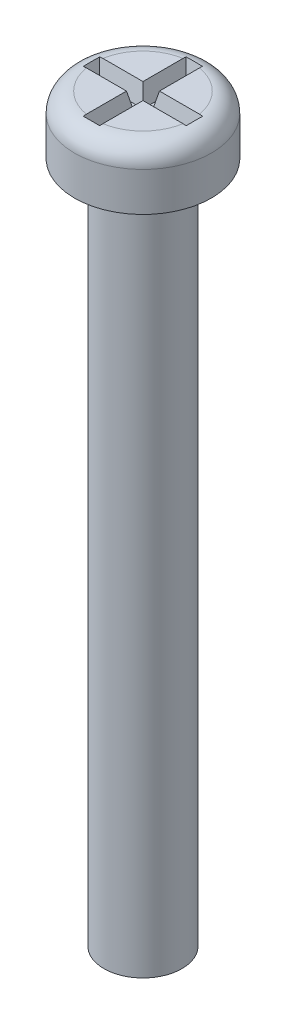
SolidWorks part; units mm, degrees
ref_plane "Спереди" through (0, 0, 0) normal (0, 0, 1) x (1, 0, 0)
ref_plane "Сверху" through (0, 0, 0) normal (0, 1, 0) x (1, 0, 0)
ref_plane "Справа" through (0, 0, 0) normal (1, 0, 0) x (0, 0, -1)
sketch "Эскиз1" plane through (0, 0, 0) normal (0, 1, 0) x (1, 0, 0)
  circle A0 centre (0, 0) radius 2
extrude "Бобышка-Вытянуть1" add sketch "Эскиз1" along normal blind 35
sketch "Эскиз2" plane through (0, 35, 0) normal (0, 1, 0) x (1, 0, 0)
  circle A0 centre (0, 0) radius 3.515
extrude "Бобышка-Вытянуть2" add sketch "Эскиз2" along normal blind 3
sketch "Эскиз3" plane through (0, 38, 0) normal (0, 1, 0) x (1, 0, 0)
  line L0 (-2.6415, 0.4228) -> (-0.4228, 0.4228)
  line L2 (-2.6415, -0.4228) -> (-2.6415, 0.4228)
  line L4 (2.6415, -0.4228) -> (2.6415, 0.4228)
  line L5 (-2.6415, -0.4228) -> (2.6415, 0.4228) construction
  line L6 (-2.6415, 0.4228) -> (2.6415, -0.4228) construction
  line L7 (-0.4228, -2.6415) -> (0.4228, -2.6415)
  line L9 (-0.4228, 2.6415) -> (0.4228, 2.6415)
  line L11 (-0.4228, -2.6415) -> (0.4228, 2.6415) construction
  line L12 (-0.4228, 2.6415) -> (0.4228, -2.6415) construction
  line L13 (-0.4228, 0.4228) -> (-0.4228, 2.6415)
  line L14 (0.4228, 2.6415) -> (0.4228, 0.4228)
  line L15 (0.4228, 0.4228) -> (2.6415, 0.4228)
  line L16 (2.6415, -0.4228) -> (0.4228, -0.4228)
  line L17 (0.4228, -0.4228) -> (0.4228, -2.6415)
  line L18 (-0.4228, -2.6415) -> (-0.4228, -0.4228)
  line L19 (-0.4228, -0.4228) -> (-2.6415, -0.4228)
  point P0 (0, 0)
  point P6 (0, 0)
extrude "Вырез-Вытянуть1" cut sketch "Эскиз3" against normal blind 1 draft 12
fillet "Скругление2" radius 1 1 edges at (0, 38, 3.515)
